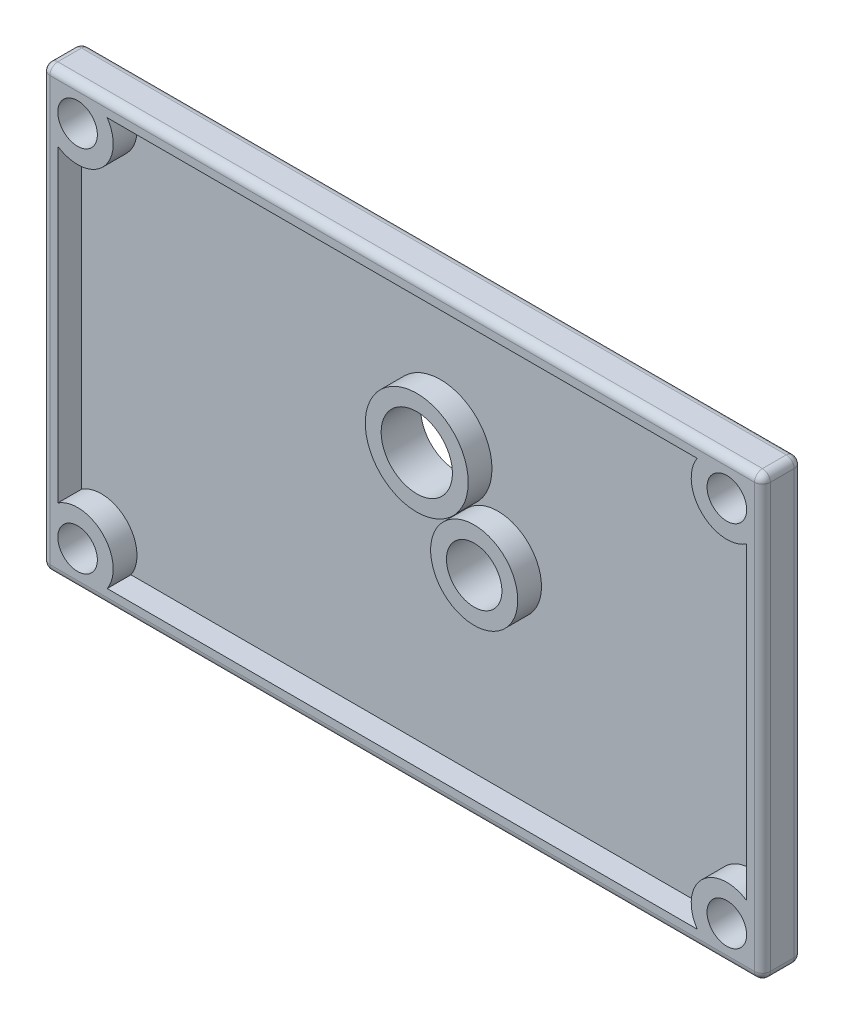
SolidWorks part; units mm, degrees
ref_plane "Front Plane" through (0, 0, 0) normal (0, 0, 1) x (1, 0, 0)
ref_plane "Top Plane" through (0, 0, 0) normal (0, 1, 0) x (1, 0, 0)
ref_plane "Right Plane" through (0, 0, 0) normal (1, 0, 0) x (0, 0, -1)
sketch "Sketch1" plane through (0, 0, 0) normal (0, 0, 1) x (1, 0, 0)
  line L1 (0, 0) -> (91, 0)
  line L2 (0, 0) -> (0, -55.5)
  line L3 (0, -55.5) -> (91, -55.5)
  line L4 (91, 0) -> (91, -55.5)
  point P8 (86.05, -4.7238)
  point P11 (6.1121, -51.0404)
  point P14 (87.0265, -51.3194)
  point P17 (44.7557, -40.2983)
  point P20 (52.8471, -15.4659)
  point P21 (0, 0)
  dimension "D1" = 55.5
  dimension "D2" = 91
extrude "Boss-Extrude1" add sketch "Sketch1" along normal blind 5 contours L1 L4 L3 L2
fillet "Fillet1" radius 1 7 edges at (0, 0, 2.5) (0, -27.75, 5) (0, -27.75, 0) (45.5, -55.5, 5) (91, -55.5, 2.5) (45.5, -55.5, 0) (0, -55.5, 2.5)
fillet "Fillet2" radius 1 9 edges at (90.7071, -55.2071, 0.2929) (90.7071, -55.2071, 4.7071) (0.2929, -0.2929, 4.7071) (0.2929, -0.2929, 0.2929) (91, -27.25, 0) (91, -27.25, 5) (46, 0, 5) (46, 0, 0) (91, 0, 2.5)
sketch "Sketch3" plane through (0, 0, 0) normal (0, 0, -1) x (-1, 0, 0)
  line L0 (-90, -55.5) -> (-1, -55.5) construction
  line L1 (0, -54.5) -> (0, -1) construction
  line L2 (-91, -1) -> (-91, -54.5) construction
  line L3 (-1, 0) -> (-90, 0) construction
  circle A0 centre (-4.5, -51) radius 2.5
  circle A1 centre (-47.3375, -19.0945) radius 4.5
  circle A2 centre (-4.5, -4.5) radius 2.5
  circle A3 centre (-54.5907, -28.8622) radius 3.5
  circle A4 centre (-86.5, -4.5) radius 2.5
  circle A5 centre (-86.5, -51) radius 2.5
  point P4 (-89.5995, -50.525)
  point P5 (-86.0212, -50.6218)
  point P8 (-4.7854, -4.5881)
  point P13 (-86.1179, -4.8782)
  point P14 (-47.3375, -19.0945)
  point P17 (-54.5907, -28.8622)
  point P18 (0, 0)
  point P19 (0, 0)
  point P20 (0, 0)
  dimension "D1" = 4.5
  dimension "D2" = 4.5
  dimension "D3" = 4.5
  dimension "D4" = 4.5
  dimension "D5" = 4.5
  dimension "D6" = 4.5
  dimension "D7" = 4.5
  dimension "D8" = 4.5
extrude "Cut-Extrude6" cut sketch "Sketch3" against normal blind 5
shell "Shell3" thickness 2 removed face at (84, -51, 5)
